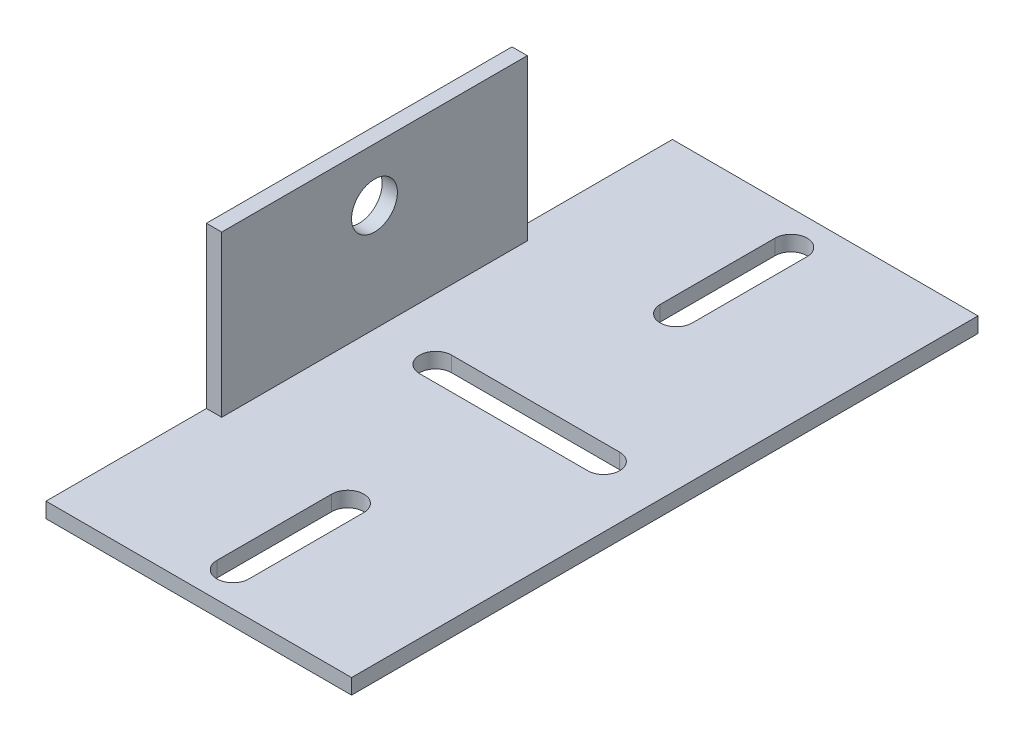
SolidWorks part; units mm, degrees
ref_plane "Спереди" through (0, 0, 0) normal (0, 0, 1) x (1, 0, 0)
ref_plane "Сверху" through (0, 0, 0) normal (0, 1, 0) x (1, 0, 0)
ref_plane "Справа" through (0, 0, 0) normal (1, 0, 0) x (0, 0, -1)
sketch "Эскиз2" plane through (0, 0, 0) normal (0, 0, 1) x (1, 0, 0)
  line L0 (0, 23) -> (0, 0)
  line L1 (0, 0) -> (40, 0)
extrude "Вытянуть-Тонкостенный1" add sketch "Эскиз2" along normal blind 82 thin thin type one direction reverse wall 2
sketch "Эскиз3" plane through (0, 2, 0) normal (0, 1, 0) x (1, 0, 0)
  line L0 (32, -38.9) -> (10, -38.9)
  line L1 (32, -43.1) -> (10, -43.1)
  line L2 (17.9, -4.4679) -> (17.9, -19.5)
  line L3 (22.1, -4.4679) -> (22.1, -19.5)
  line L4 (40, -41) -> (2, -41) construction
  line L5 (40, -82) -> (40, 0) construction
  line L6 (2, -82) -> (2, 0) construction
  line L7 (22.1, -77.5321) -> (22.1, -62.5)
  line L8 (17.9, -77.5321) -> (17.9, -62.5)
  arc A0 (32, -38.9) -> (32, -43.1) centre (32, -41) cw
  arc A1 (10, -38.9) -> (10, -43.1) centre (10, -41) ccw
  arc A2 (17.9, -4.4679) -> (22.1, -4.4679) centre (20, -4.4679) cw
  arc A3 (17.9, -19.5) -> (22.1, -19.5) centre (20, -19.5) ccw
  arc A4 (17.9, -62.5) -> (22.1, -62.5) centre (20, -62.5) cw
  arc A5 (17.9, -77.5321) -> (22.1, -77.5321) centre (20, -77.5321) ccw
  point P24 (0, 0)
  point P25 (20, -19.5)
  point P26 (20, -19.5)
  point P28 (20, -4.6993)
  point P29 (20, -4.4679)
  dimension "D1" = 20
extrude "Вырез-Вытянуть1" cut sketch "Эскиз3" against normal blind 10
sketch "Эскиз4" plane through (0, 0, 0) normal (-1, 0, 0) x (0, 0, 1)
  line L0 (41, 23) -> (41, 0) construction
  line L1 (82, 23) -> (0, 23) construction
  circle A0 centre (41, 16) radius 3
extrude "Вырез-Вытянуть2" cut sketch "Эскиз4" against normal blind 10
sketch "Эскиз5" plane through (0, 0, 0) normal (-1, 0, 0) x (0, 0, 1)
  line L0 (41, 23) -> (41, -0.8996) construction
  line L1 (0, 23) -> (21, 23)
  line L2 (0, 23) -> (0, 2)
  line L3 (0, 2) -> (21, 2)
  line L4 (21, 23) -> (21, 2)
  line L5 (82, 23) -> (0, 23) construction
  line L6 (61, 23) -> (61, 2)
  line L7 (82, 2) -> (61, 2)
  line L8 (82, 23) -> (82, 2)
  line L9 (82, 23) -> (61, 23)
extrude "Вырез-Вытянуть3" cut sketch "Эскиз5" against normal blind 10
